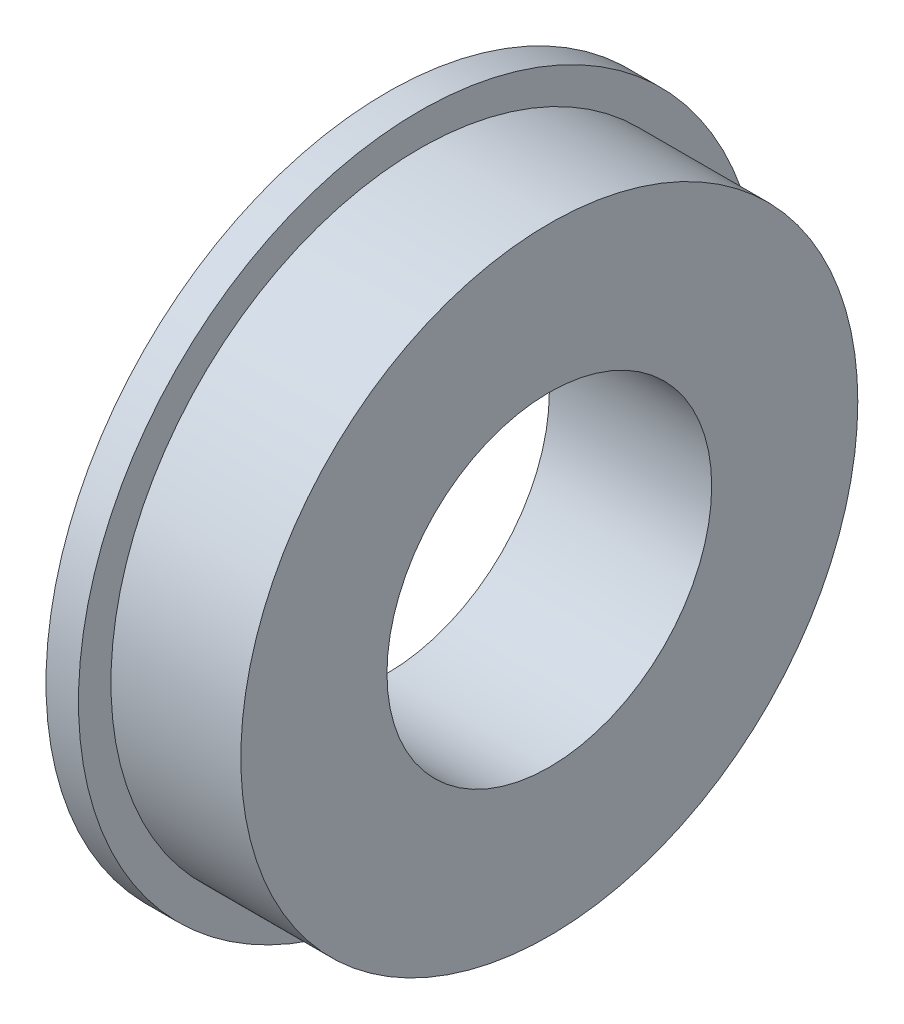
SolidWorks part; units mm, degrees
ref_plane "Front Plane" through (0, 0, 0) normal (0, 0, 1) x (1, 0, 0)
ref_plane "Top Plane" through (0, 0, 0) normal (0, 1, 0) x (1, 0, 0)
ref_plane "Right Plane" through (0, 0, 0) normal (1, 0, 0) x (0, 0, -1)
sketch "Sketch1" plane through (0, 0, 0) normal (1, 0, 0) x (0, 0, -1)
  circle A0 centre (0, 0) radius 9.5
  circle A1 centre (0, 0) radius 10.5
  circle A2 centre (0, 0) radius 5
  dimension "D1" = 10
  dimension "D2" = 19
  dimension "D3" = 21
extrude "Boss-Extrude1" add sketch "Sketch1" along normal blind 5 contours A0 A2 region at (0, 0, 9.2313)
extrude "Boss-Extrude2" add sketch "Sketch1<3>" along normal blind 1 contours A1 A0 region at (0, 0, 10.203)
sketch "Sketch1<3>" plane through (0, 0, 0) normal (1, 0, 0) x (0, 0, -1) same geometry as "Sketch1"
